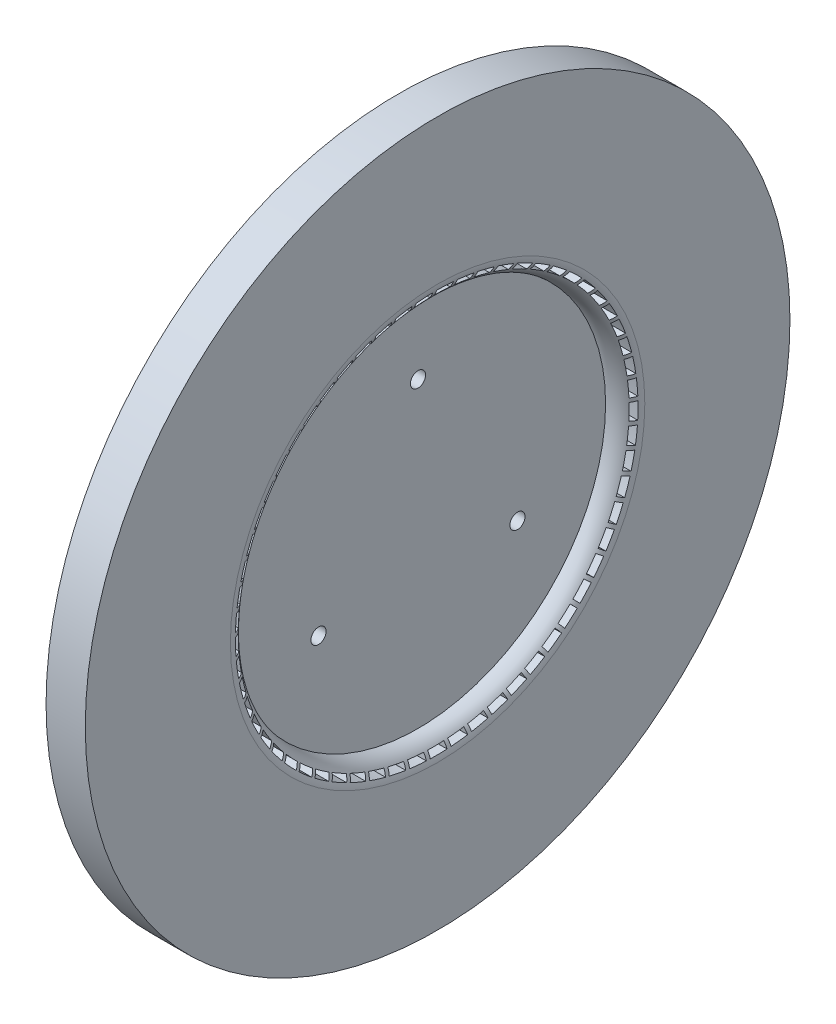
SolidWorks part; units mm, degrees
ref_plane "Front Plane" through (0, 0, 0) normal (0, 0, 1) x (1, 0, 0)
ref_plane "Top Plane" through (0, 0, 0) normal (0, 1, 0) x (1, 0, 0)
ref_plane "Right Plane" through (0, 0, 0) normal (1, 0, 0) x (0, 0, -1)
sketch "Sketch1" plane through (0, 0, 0) normal (1, 0, 0) x (0, 0, -1)
  circle A0 centre (0, 0) radius 89.825
  circle A5 centre (0, 0) radius 47.825
  dimension "D1" = 179.65
  dimension "D2" = 95.65
extrude "Flange" add sketch "Sketch1" along normal blind 10
sketch "Sketch2" plane through (10, 0, 0) normal (1, 0, 0) x (0, 0, -1)
  line L0 (0, 49.825) -> (0, 51.325)
  line L1 (-1, 49.815) -> (-1, 51.3153)
  line L2 (5.1231, 49.5609) -> (5.2773, 51.053)
  line L3 (4.1273, 49.6538) -> (4.2816, 51.1461)
  line L4 (10.1918, 48.7715) -> (10.4986, 50.2398)
  line L5 (9.2109, 48.9662) -> (9.5178, 50.4348)
  line L6 (15.1525, 47.4651) -> (15.6087, 48.894)
  line L7 (14.1968, 47.7596) -> (14.6531, 49.1888)
  line L8 (19.9526, 45.6555) -> (20.5533, 47.03)
  line L9 (19.0323, 46.0467) -> (19.6331, 47.4215)
  line L10 (24.5412, 43.362) -> (25.28, 44.6674)
  line L11 (23.666, 43.8458) -> (24.4049, 45.1515)
  line L12 (28.8697, 40.6088) -> (29.7388, 41.8313)
  line L13 (28.0488, 41.18) -> (28.9181, 42.4028)
  line L14 (32.8921, 37.4251) -> (33.8823, 38.5518)
  line L15 (32.1343, 38.0778) -> (33.1247, 39.2047)
  line L16 (36.5658, 33.8448) -> (37.6667, 34.8637)
  line L17 (35.8792, 34.5719) -> (36.9802, 35.591)
  line L18 (39.852, 29.9057) -> (41.0517, 30.806)
  line L19 (39.2437, 30.6995) -> (40.4437, 31.6)
  line L20 (42.7157, 25.6496) -> (44.0017, 26.4217)
  line L21 (42.1923, 26.5017) -> (43.4785, 27.274)
  line L22 (45.1266, 21.1215) -> (46.4852, 21.7574)
  line L23 (44.6936, 22.023) -> (46.0524, 22.659)
  line L24 (47.0592, 16.3696) -> (48.4759, 16.8624)
  line L25 (46.7212, 17.3108) -> (48.1382, 17.8037)
  line L26 (48.4929, 11.4442) -> (49.9528, 11.7887)
  line L27 (48.2534, 12.4152) -> (49.7136, 12.7597)
  line L28 (49.4126, 6.3974) -> (50.9002, 6.59)
  line L29 (49.2742, 7.3879) -> (50.7621, 7.5805)
  line L30 (49.8085, 1.2829) -> (51.308, 1.3215)
  line L31 (49.7727, 2.2823) -> (51.2725, 2.3209)
  line L32 (49.6764, -3.8453) -> (51.1719, -3.961)
  line L33 (49.7436, -2.8475) -> (51.2394, -2.9633)
  line L34 (49.0177, -8.9327) -> (50.4934, -9.2016)
  line L35 (49.1871, -7.9471) -> (50.6631, -8.216)
  line L36 (47.8395, -13.9254) -> (49.2797, -14.3446)
  line L37 (48.1093, -12.9624) -> (49.5498, -13.3817)
  line L38 (46.1541, -18.7705) -> (47.5436, -19.3356)
  line L39 (46.5215, -17.8404) -> (47.9113, -18.4056)
  line L40 (43.9795, -23.4166) -> (45.3035, -24.1216)
  line L41 (44.4406, -22.5292) -> (45.7649, -23.2343)
  line L42 (41.3387, -27.8145) -> (42.5832, -28.6519)
  line L43 (41.8886, -26.9792) -> (43.1333, -27.8167)
  line L44 (38.2596, -31.9176) -> (39.4115, -32.8784)
  line L45 (38.8925, -31.1432) -> (40.0446, -32.1043)
  line L46 (34.7751, -35.6823) -> (35.822, -36.7565)
  line L47 (35.4842, -34.9772) -> (36.5313, -36.0516)
  line L48 (30.9219, -39.0688) -> (31.8528, -40.2449)
  line L49 (31.6998, -38.4403) -> (32.6309, -39.6167)
  line L50 (26.7409, -42.0411) -> (27.5459, -43.3068)
  line L51 (27.5793, -41.496) -> (28.3845, -42.7619)
  line L52 (22.2764, -44.5678) -> (22.9471, -45.9095)
  line L53 (23.1664, -44.1117) -> (23.8372, -45.4537)
  line L54 (17.5759, -46.6221) -> (18.105, -48.0257)
  line L55 (18.508, -46.2599) -> (19.0373, -47.6638)
  line L56 (12.689, -48.1822) -> (13.071, -49.6327)
  line L57 (13.6535, -47.9178) -> (14.0355, -49.3686)
  line L58 (7.6676, -49.2315) -> (7.8984, -50.7136)
  line L59 (8.6541, -49.0677) -> (8.885, -50.5501)
  line L60 (2.5649, -49.7589) -> (2.6421, -51.2569)
  line L61 (3.5631, -49.6974) -> (3.6403, -51.1957)
  line L62 (-2.5649, -49.7589) -> (-2.6421, -51.2569)
  line L63 (-1.5657, -49.8004) -> (-1.643, -51.2987)
  line L64 (-7.6676, -49.2315) -> (-7.8984, -50.7136)
  line L65 (-6.678, -49.3755) -> (-6.9088, -50.8579)
  line L66 (-12.689, -48.1822) -> (-13.071, -49.6327)
  line L67 (-11.7194, -48.4271) -> (-12.1015, -49.8779)
  line L68 (-17.5759, -46.6221) -> (-18.105, -48.0257)
  line L69 (-16.6366, -46.9655) -> (-17.1658, -48.3693)
  line L70 (-22.2764, -44.5678) -> (-22.9471, -45.9095)
  line L71 (-21.3775, -45.0059) -> (-22.0482, -46.3479)
  line L72 (-26.7409, -42.0411) -> (-27.5459, -43.3068)
  line L73 (-25.8917, -42.5693) -> (-26.6969, -43.8353)
  line L74 (-30.9219, -39.0688) -> (-31.8528, -40.2449)
  line L75 (-30.1315, -39.6815) -> (-31.0626, -40.8579)
  line L76 (-34.7751, -35.6823) -> (-35.822, -36.7565)
  line L77 (-34.0519, -36.373) -> (-35.099, -37.4475)
  line L78 (-38.2596, -31.9176) -> (-39.4115, -32.8784)
  line L79 (-37.6113, -32.679) -> (-38.7634, -33.6401)
  line L80 (-41.3387, -27.8145) -> (-42.5832, -28.6519)
  line L81 (-40.7721, -28.6386) -> (-42.0168, -29.4761)
  line L82 (-43.9795, -23.4166) -> (-45.3035, -24.1216)
  line L83 (-43.5006, -24.2946) -> (-44.8249, -24.9997)
  line L84 (-46.1541, -18.7705) -> (-47.5436, -19.3356)
  line L85 (-45.7681, -19.693) -> (-47.1578, -20.2582)
  line L86 (-47.8395, -13.9254) -> (-49.2797, -14.3446)
  line L87 (-47.5503, -14.8827) -> (-48.9909, -15.302)
  line L88 (-49.0177, -8.9327) -> (-50.4934, -9.2016)
  line L89 (-48.8286, -9.9147) -> (-50.3046, -10.1836)
  line L90 (-49.6764, -3.8453) -> (-51.1719, -3.961)
  line L91 (-49.5892, -4.8415) -> (-51.085, -4.9573)
  line L92 (-49.8085, 1.2829) -> (-51.308, 1.3215)
  line L93 (-49.8242, 0.283) -> (-51.324, 0.3216)
  line L94 (-49.4126, 6.3974) -> (-50.9002, 6.59)
  line L95 (-49.531, 5.4044) -> (-51.0189, 5.5971)
  line L96 (-48.4929, 11.4442) -> (-49.9528, 11.7887)
  line L97 (-48.7128, 10.4686) -> (-50.173, 10.8132)
  line L98 (-47.0592, 16.3696) -> (-48.4759, 16.8624)
  line L99 (-47.3782, 15.4218) -> (-48.7953, 15.9147)
  line L100 (-45.1266, 21.1215) -> (-46.4852, 21.7574)
  line L101 (-45.5414, 20.2116) -> (-46.9003, 20.8476)
  line L102 (-42.7157, 25.6496) -> (-44.0017, 26.4217)
  line L103 (-43.2219, 24.7871) -> (-44.5081, 25.5594)
  line L104 (-39.852, 29.9057) -> (-41.0517, 30.806)
  line L105 (-40.4442, 29.0998) -> (-41.6442, 30.0003)
  line L106 (-36.5658, 33.8448) -> (-37.6667, 34.8637)
  line L107 (-37.2377, 33.1041) -> (-38.3388, 34.1232)
  line L108 (-32.8921, 37.4251) -> (-33.8823, 38.5518)
  line L109 (-33.6366, 36.7575) -> (-34.627, 37.8844)
  line L110 (-28.8697, 40.6088) -> (-29.7388, 41.8313)
  line L111 (-29.6789, 40.0212) -> (-30.5482, 41.244)
  line L112 (-24.5412, 43.362) -> (-25.28, 44.6674)
  line L113 (-25.4065, 42.8607) -> (-26.1455, 44.1664)
  line L114 (-19.9526, 45.6555) -> (-20.5533, 47.03)
  line L115 (-20.8649, 45.2458) -> (-21.4657, 46.6206)
  line L116 (-15.1525, 47.4651) -> (-15.6087, 48.894)
  line L117 (-16.1021, 47.1514) -> (-16.5584, 48.5806)
  line L118 (-10.1918, 48.7715) -> (-10.4986, 50.2398)
  line L119 (-11.1686, 48.5571) -> (-11.4755, 50.0257)
  line L120 (-5.1231, 49.5609) -> (-5.2773, 51.053)
  line L121 (-6.1167, 49.4481) -> (-6.271, 50.9405)
  circle A0 centre (0, 0) radius 49.825
  circle A1 centre (0, 0) radius 51.325
  circle A2 centre (0, 0) radius 47.825 construction
  point P10 (0, 0)
  point P11 (0, 0)
  point P253 (0, 0)
  dimension "D2" = 1.5
  dimension "D3" = 2
  dimension "D4" = 61
extrude "Regen Slots" cut sketch "Sketch2" against normal blind 25 contours L117 A1 L114 A0 | L119 A1 L116 A0 | L121 A1 L118 A0 | L1 A1 L120 A0 | L3 A1 L0 A0 | L5 A1 L2 A0 | L7 A1 L4 A0 | L9 A1 L6 A0 | L11 A1 L8 A0 | L13 A1 L10 A0 | L15 A1 L12 A0 | L17 A1 L14 A0 | L19 A1 L16 A0 | L21 A1 L18 A0 | L23 A1 L20 A0 | L25 A1 L22 A0 | L27 A1 L24 A0 | L29 A1 L26 A0 | L31 A1 L28 A0 | L33 A1 L30 A0 | L35 A1 L32 A0 | L37 A1 L34 A0 | L39 A1 L36 A0 | L41 A1 L38 A0 | L43 A1 L40 A0 | L45 A1 L42 A0 | L47 A1 L44 A0 | L49 A1 L46 A0 | L51 A1 L48 A0 | L53 A1 L50 A0 | L55 A1 L52 A0 | L57 A1 L54 A0 | L59 A1 L56 A0 | L61 A1 L58 A0 | L63 A1 L60 A0 | L65 A1 L62 A0 | L67 A1 L64 A0 | L69 A1 L66 A0 | L71 A1 L68 A0 | L73 A1 L70 A0 | L75 A1 L72 A0 | L77 A1 L74 A0 | L79 A1 L76 A0 | L81 A1 L78 A0 | L83 A1 L80 A0 | L85 A1 L82 A0 | L87 A1 L84 A0 | L89 A1 L86 A0 | L91 A1 L88 A0 | L93 A1 L90 A0 | L95 A1 L92 A0 | L97 A1 L94 A0 | L99 A1 L96 A0 | L101 A1 L98 A0 | L103 A1 L100 A0 | L107 A1 L104 A0 | L109 A1 L106 A0 | L111 A1 L108 A0 | L113 A1 L110 A0 | L115 A1 L112 A0 | L105 A1 L102 A0
sketch "Sketch3" plane through (0, 0, 0) normal (-1, 0, 0) x (0, 0, 1)
  circle A0 centre (0, 0) radius 47.825
  dimension "D1" = 95.65
extrude "Faceplate Extrusion to Manifold" add sketch "Sketch3" against normal blind 5 separate body
sketch "Sketch4" plane through (0, 0, 0) normal (-1, 0, 0) x (0, 0, 1)
  circle A0 centre (0, 0) radius 47.825
  dimension "D1" = 95.65
extrude "Faceplate Extrusion to Chamber" add sketch "Sketch4" along normal blind 5
fillet "Regen Fillet" radius 5 1 edges at (10, 0, -47.825)
sketch "Sketch5" plane through (-5, 0, 0) normal (-1, 0, 0) x (0, 0, 1)
  circle A0 centre (0, 0) radius 47.825
  circle A1 centre (0, 0) radius 44.825
  dimension "D1" = 95.65
  dimension "D2" = 3
extrude "O-Ring Slot" cut sketch "Sketch5" against normal blind 6.5
sketch "Sketch6" plane through (-5, 0, 0) normal (-1, 0, 0) x (0, 0, 1)
  circle A0 centre (0, 38.3209) radius 1.1946 construction
  circle A1 centre (0, 29.2826) radius 1.9319
  circle A2 centre (0, 20.2443) radius 1.1946 construction
  circle A3 centre (17.5321, -10.1222) radius 1.1946 construction
  circle A4 centre (25.3595, -14.6413) radius 1.9319
  circle A5 centre (33.1869, -19.1604) radius 1.1946 construction
  circle A6 centre (-17.5321, -10.1222) radius 1.1946 construction
  circle A7 centre (-25.3595, -14.6413) radius 1.9319
  circle A8 centre (-33.1869, -19.1604) radius 1.1946 construction
  point P6 (16.9531, -20.9364)
  point P7 (0, 0)
  point P22 (0, 0)
  dimension "D1" = 2.3891
  dimension "D2" = 3.8638
  dimension "D5" = 29.2826
  dimension "D3" = 9.0383
  dimension "D4" = 9.0383
  dimension "D6" = 3
extrude "Fuel Orifices" cut sketch "Sketch6" against normal through all
equation "\"Flange_Dia\"= 179.65"
equation "\"D1@Sketch1\"=\"Flange_Dia\""
equation "\"Regen_Thickness\"= 1.5"
equation "\"Regen_To_Inner\"=2"
equation "\"Faceplate_Area\"=95.65"
equation "\"Regen_Rib_Thickness\"=1"
equation "\"D2@Sketch1\"=\"Faceplate_Area\""
equation "\"Flange_Thickness\"= 10"
equation "\"D1@Flange\" = \"Flange_Thickness\""
equation "\"D1@Sketch2\"=\"Regen_Rib_Thickness\""
equation "\"D2@Sketch2\"=\"Regen_Thickness\""
equation "\"D3@Sketch2\"=\"Regen_To_Inner\""
equation "\"D1@Sketch3\"=\"Faceplate_Area\""
equation "\"D1@Faceplate Extrusion to Manifold\" = \"Flange_Thickness\" / 2"
equation "\"D1@Sketch4\"=\"Faceplate_Area\""
equation "\"Faceplate_To_Chamber_Extrusion\"=5"
equation "\"D1@Faceplate Extrusion to Chamber\"=\"Faceplate_To_Chamber_Extrusion\""
equation "\"D1@Sketch5\"=\"Faceplate_Area\""
equation "\"Injector_MCCN_O-Ring\"=3"
equation "\"D2@Sketch5\"=\"Injector_MCCN_O-Ring\""
equation "\"D1@O-Ring Slot\" =  ( \"Faceplate_To_Chamber_Extrusion\" )  +  ( \"Injector_MCCN_O-Ring\" / 2 ) "
equation "\"Ox_Orifice\"=2.38915"
equation "\"D1@Sketch6\"=\"Ox_Orifice\""
equation "\"Fuel_Orifice\"=3.86377"
equation "\"D2@Sketch6\"=\"Fuel_Orifice\""
equation "\"OxFuel_Dist\"=9.03829"
equation "\"Fuel_Dist_From_Center\"=29.2826"
equation "\"D5@Sketch6\"=\"Fuel_Dist_From_Center\""
equation "\"D3@Sketch6\"=\"OxFuel_Dist\""
equation "\"D4@Sketch6\"=\"OxFuel_Dist\""
